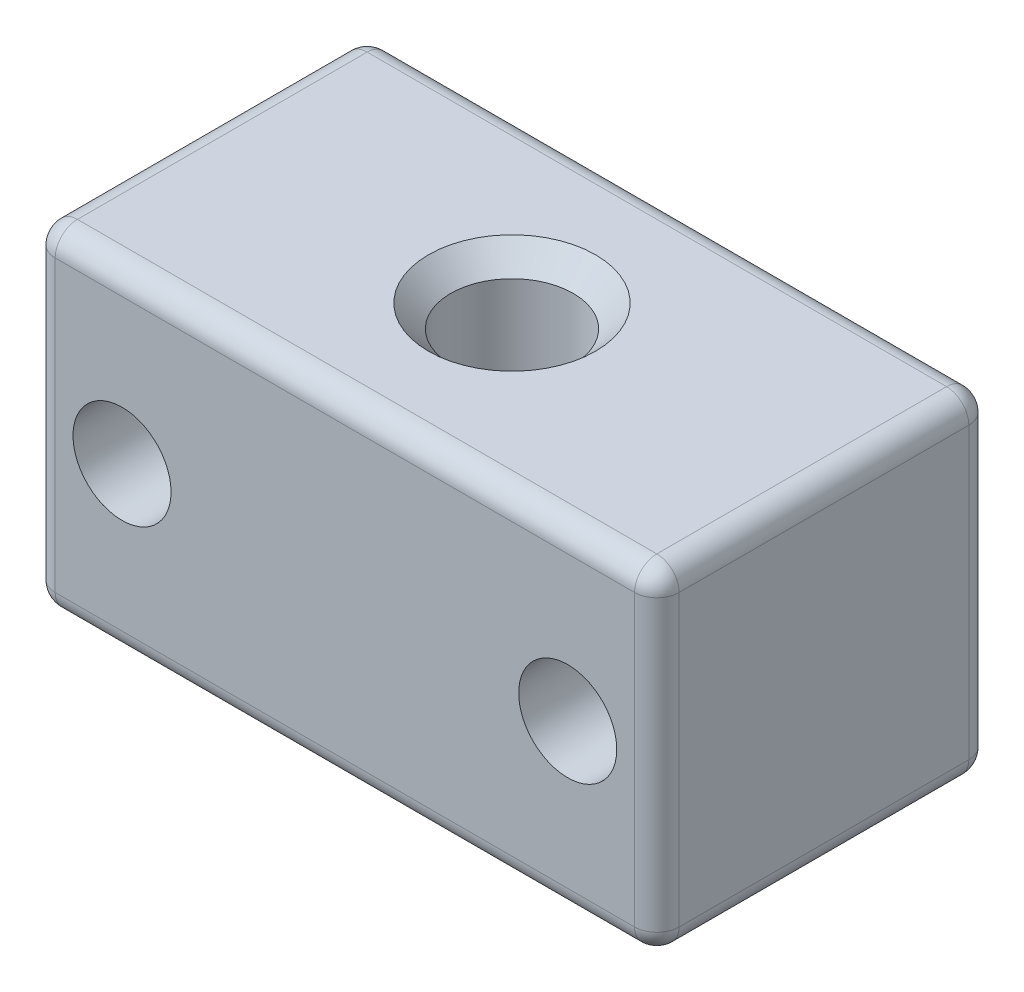
SolidWorks part; units mm, degrees
ref_plane "前视基准面" through (0, 0, 0) normal (0, 0, 1) x (1, 0, 0)
ref_plane "上视基准面" through (0, 0, 0) normal (0, 1, 0) x (1, 0, 0)
ref_plane "右视基准面" through (0, 0, 0) normal (1, 0, 0) x (0, 0, -1)
other "Configuration Table"
sketch "草图1" plane through (0, 0, 0) normal (0, 1, 0) x (1, 0, 0)
  line L1 (-14, -7.5) -> (14, -7.5)
  line L2 (-14, -7.5) -> (-14, 7.5)
  line L3 (-14, 7.5) -> (14, 7.5)
  line L4 (14, -7.5) -> (14, 7.5)
  line L5 (-14, -7.5) -> (14, 7.5) construction
  line L6 (-14, 7.5) -> (14, -7.5) construction
  circle A0 centre (0, 0) radius 2.75
  point P0 (0, 0)
  dimension "D3" = 5.5
  dimension "D1" = 28
  dimension "D2" = 15
extrude "凸台-拉伸1" add sketch "草图1" along normal mid plane 15
sketch "草图2" plane through (0, 0, 7.5) normal (0, 0, 1) x (1, 0, 0)
  circle A0 centre (-10, 0) radius 2.2
  circle A1 centre (10, 0) radius 2.2
  dimension "D1" = 4.4
  dimension "D2" = 20
  dimension "D3" = 10
extrude "切除-拉伸1" cut sketch "草图2" against normal blind 15
fillet "圆角1" radius 1 12 edges at (14, 0, 7.5) (14, 7.5, 0) (14, 0, -7.5) (14, -7.5, 0) (-14, 0, -7.5) (-14, 7.5, 0) (-14, 0, 7.5) (-14, -7.5, 0) (0, -7.5, -7.5) (0, -7.5, 7.5) (0, 7.5, -7.5) (0, 7.5, 7.5)
chamfer "倒角1" distance 1 angle 45 2 edges at (0, -7.5, 2.75) (0, 7.5, 2.75)
